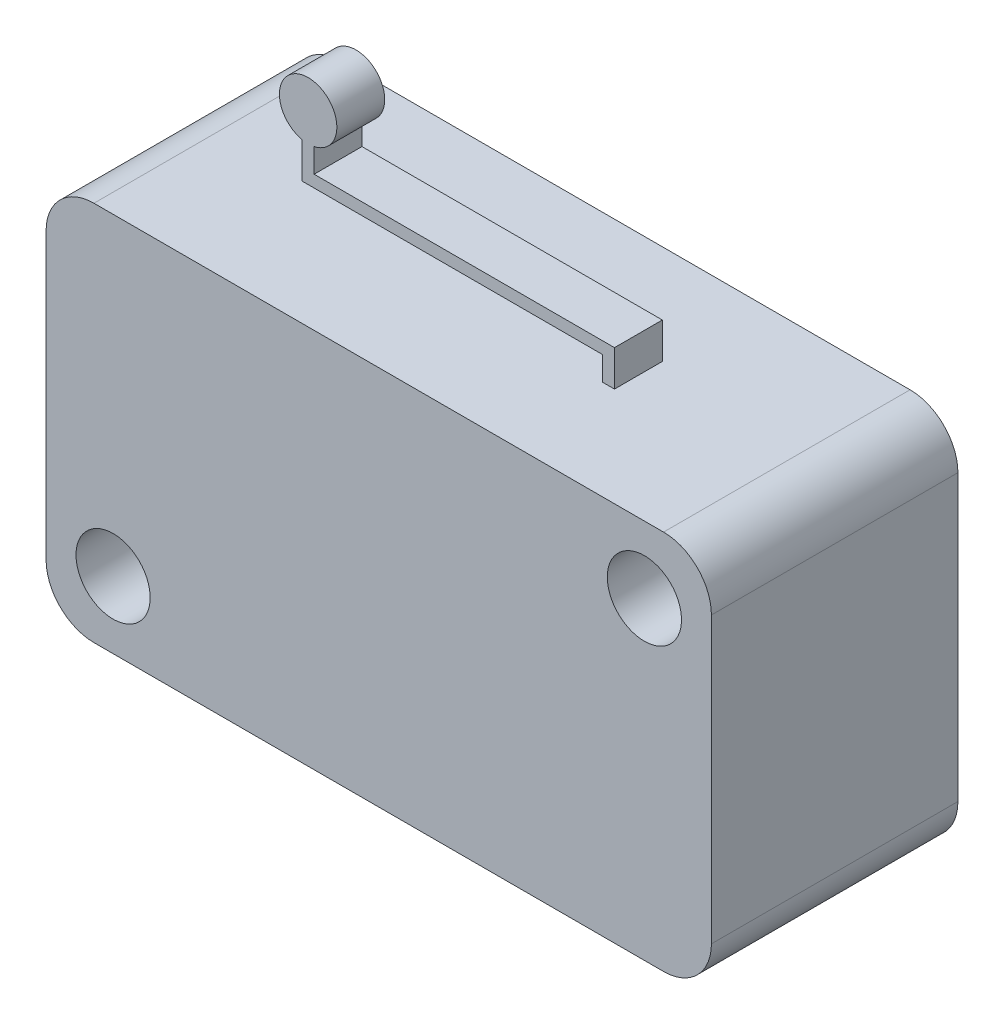
SolidWorks part; units mm, degrees
ref_plane "Front Plane" through (0, 0, 0) normal (0, 0, 1) x (1, 0, 0)
ref_plane "Top Plane" through (0, 0, 0) normal (0, 1, 0) x (1, 0, 0)
ref_plane "Right Plane" through (0, 0, 0) normal (1, 0, 0) x (0, 0, -1)
sketch "Sketch1" plane through (0, 0, 0) normal (0, 0, 1) x (1, 0, 0)
  line L0 (2.8, 2.8) -> (25, 2.8) construction
  line L1 (2, 0) -> (25.8, 0)
  line L2 (0, 2) -> (0, 13.9)
  line L3 (2, 15.9) -> (25.8, 15.9)
  line L4 (27.8, 2) -> (27.8, 13.9)
  line L5 (25, 2.8) -> (25, 13.1) construction
  line L6 (25, 13.1) -> (2.8, 13.1) construction
  line L7 (2.8, 13.1) -> (2.8, 2.8) construction
  arc A0 (2, 0) -> (0, 2) centre (2, 2) cw
  arc A1 (27.8, 2) -> (25.8, 0) centre (25.8, 2) cw
  arc A2 (27.8, 13.9) -> (25.8, 15.9) centre (25.8, 13.9) ccw
  arc A3 (2, 15.9) -> (0, 13.9) centre (2, 13.9) ccw
  circle A4 centre (2.8, 2.8) radius 1.55
  circle A5 centre (25, 13.1) radius 1.55
  point P7 (0, 0)
  point P10 (27.8, 0)
  point P15 (0, 15.9)
  point P20 (13.9, 2.8)
  point P23 (13.9, 0)
  point P24 (25, 7.95)
  point P25 (27.8, 7.95)
  dimension "D3" = 2
  dimension "D5" = 3.1
  dimension "D1" = 27.8
  dimension "D2" = 15.9
  dimension "D4" = 22.2
  dimension "D6" = 10.3
extrude "Boss-Extrude1" add sketch "Sketch1" along normal blind 10.3
ref_plane "Plane1" through (0, 0, 5.15) normal (0, 0, 1) x (1, 0, 0)
sketch "Sketch2" plane through (0, 0, 5.15) normal (0, 0, 1) x (1, 0, 0)
  line L0 (6.55, 18.4) -> (6.55, 16.9)
  line L2 (6.55, 16.9) -> (7.05, 16.9)
  line L3 (7.05, 18.4) -> (7.05, 17.4)
  line L4 (7.05, 16.9) -> (19.1, 16.9)
  line L6 (19.6, 17.4) -> (7.05, 17.4)
  line L7 (19.1, 16.9) -> (19.1, 15.9)
  line L8 (19.1, 15.9) -> (19.6, 15.9)
  line L9 (19.6, 15.9) -> (19.6, 17.4)
  line L11 (25.8, 15.9) -> (2, 15.9) construction
  line L12 (6.55, 17.65) -> (7.05, 17.65) construction
  line L13 (27.8, 2) -> (27.8, 13.9) construction
  arc A0 (7.05, 18.4) -> (6.55, 18.4) centre (6.8, 19.5737) ccw
  point P1 (6.8584, 19.5737)
  point P11 (6.8, 17.65)
  point P13 (6.8, 16.9)
  dimension "D1" = 2.4
  dimension "D2" = 0.5
  dimension "D3" = 0.5
  dimension "D4" = 0.5
  dimension "D5" = 12.8
  dimension "D6" = 8.2
  dimension "D7" = 1
  dimension "D8" = 1.5
extrude "Boss-Extrude2" add sketch "Sketch2" along normal blind 1 and the other way blind 1
